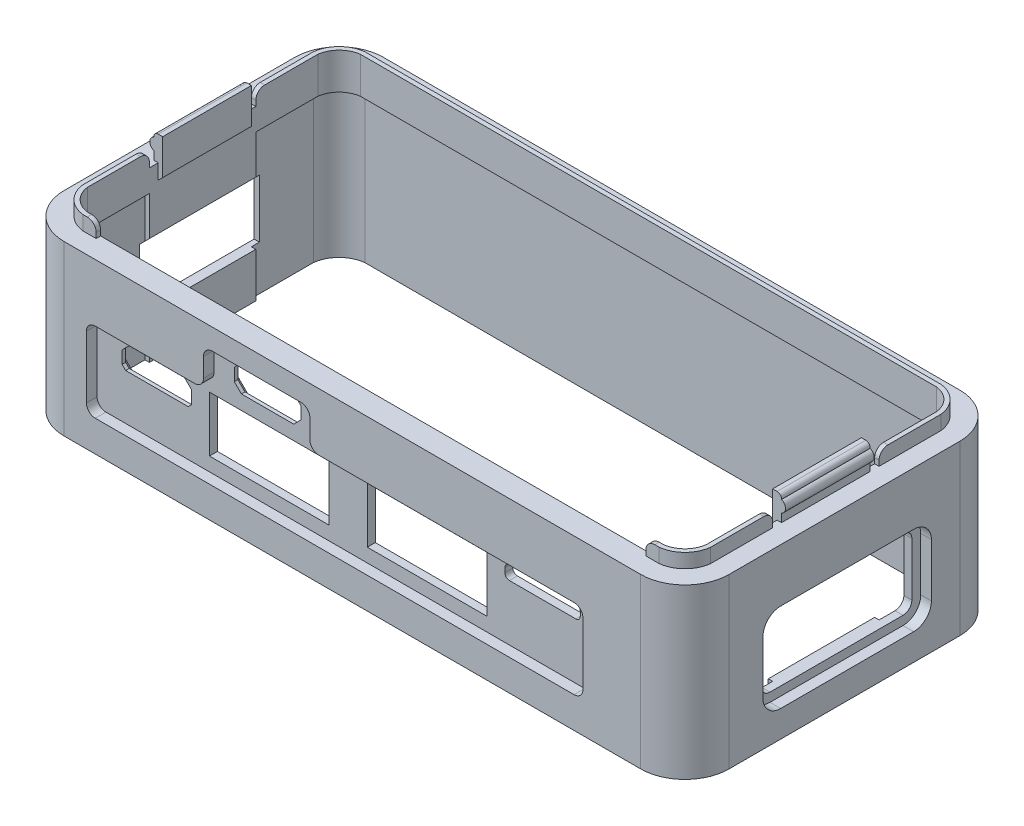
SolidWorks part; units mm, degrees
ref_plane "前视基准面" through (0, 0, 0) normal (0, 0, 1) x (1, 0, 0)
ref_plane "上视基准面" through (0, 0, 0) normal (0, 1, 0) x (1, 0, 0)
ref_plane "右视基准面" through (0, 0, 0) normal (1, 0, 0) x (0, 0, -1)
sketch "zero" plane through (0, 0, 0) normal (0, 1, 0) x (1, 0, 0)
  line L1 (-29.5, 15) -> (29.5, 15)
  line L2 (-32.5, 12) -> (-32.5, -12)
  line L3 (-29.5, -15) -> (29.5, -15)
  line L4 (32.5, 12) -> (32.5, -12)
  line L5 (-32.5, 15) -> (32.5, -15) construction
  line L6 (-32.5, -15) -> (32.5, 15) construction
  line L7 (-25.7, -15) -> (-14.5, -15)
  line L8 (-25.7, -15) -> (-25.7, -9.6569)
  line L9 (-25.7, -9.6569) -> (-14.5, -9.6569)
  line L10 (-14.5, -15) -> (-14.5, -9.6569)
  line L11 (5.2, -15) -> (12.7, -15)
  line L12 (5.2, -15) -> (5.2, -11)
  line L13 (5.2, -11) -> (12.7, -11)
  line L14 (12.7, -15) -> (12.7, -11)
  line L15 (17.8, -15) -> (25.3, -15)
  line L16 (17.8, -15) -> (17.8, -11)
  line L17 (17.8, -11) -> (25.3, -11)
  line L18 (25.3, -15) -> (25.3, -11)
  line L19 (-32.5, 7.7) -> (-19.5, 7.7)
  line L20 (-32.5, 7.7) -> (-32.5, -4.3)
  line L21 (-32.5, -4.3) -> (-19.5, -4.3)
  line L22 (-19.5, 7.7) -> (-19.5, -4.3)
  line L23 (-25.5, 14) -> (25.5, 14)
  line L24 (-25.5, 14) -> (-25.5, 8.8)
  line L25 (-25.5, 8.8) -> (25.5, 8.8)
  line L26 (25.5, 14) -> (25.5, 8.8)
  line L27 (-19.5, 7.2329) -> (-35.5, 7.2329)
  line L28 (-19.5, 7.2329) -> (-19.5, -3.7671)
  line L29 (-19.5, -3.7671) -> (-35.5, -3.7671)
  line L30 (-35.5, 7.2329) -> (-35.5, -3.7671)
  arc A0 (29.5, -15) -> (32.5, -12) centre (29.5, -12) ccw
  arc A1 (29.5, 15) -> (32.5, 12) centre (29.5, 12) cw
  arc A2 (-32.5, -12) -> (-29.5, -15) centre (-29.5, -12) ccw
  arc A3 (-29.5, 15) -> (-32.5, 12) centre (-29.5, 12) ccw
  circle A4 centre (-29, 11.4) radius 3
  circle A5 centre (-29, -11.5) radius 3
  circle A6 centre (29, 11.4) radius 3
  circle A7 centre (29, -11.5) radius 3
  circle A8 centre (-29, 11.4) radius 1.375
  circle A9 centre (-29, -11.5) radius 1.375
  circle A10 centre (29, -11.5) radius 1.375
  circle A11 centre (29, 11.4) radius 1.375
  point P0 (0, 0)
  dimension "D3" = 3
  dimension "D4" = 6
  dimension "D9" = 2.75
  dimension "D1" = 65
  dimension "D2" = 30
  dimension "D5" = 3.6
  dimension "D6" = 3.5
  dimension "D7" = 3.5
  dimension "D8" = 3.5
  dimension "D10" = 12
  dimension "D11" = 7.3
  dimension "D12" = 13
  dimension "D13" = 11.2
  dimension "D14" = 6.8
  dimension "D15" = 19.7
  dimension "D16" = 7.5
  dimension "D17" = 7.5
  dimension "D18" = 5.1
  dimension "D19" = 4
  dimension "D20" = 5.2
  dimension "D21" = 7
  dimension "D22" = 7
  dimension "D23" = 1
  dimension "D24" = 11
  dimension "D25" = 16
sketch "sugar" plane through (0, 0, 0) normal (0, 1, 0) x (1, 0, 0)
  line L1 (-29.5, 15) -> (29.5, 15)
  line L2 (-32.5, 12) -> (-32.5, -12)
  line L3 (-29.5, -15) -> (29.5, -15)
  line L4 (32.5, 12) -> (32.5, -12)
  line L5 (-32.5, 15) -> (32.5, -15) construction
  line L6 (-32.5, -15) -> (32.5, 15) construction
  line L7 (23.5, -11.5) -> (19.5, -11.5)
  line L8 (23.5, -11.5) -> (23.5, -13.9082)
  line L9 (23.5, -13.9082) -> (19.5, -13.9082)
  line L10 (19.5, -11.5) -> (19.5, -13.9082)
  line L11 (16, -11.0071) -> (8.5, -11.0071)
  line L12 (16, -11.0071) -> (16, -15)
  line L13 (16, -15) -> (8.5, -15)
  line L14 (8.5, -11.0071) -> (8.5, -15)
  line L15 (20.5, -13.9082) -> (22.5, -13.9082)
  line L16 (20.5, -13.9082) -> (20.5, -14.8173)
  line L17 (20.5, -14.8173) -> (22.5, -14.8173)
  line L18 (22.5, -13.9082) -> (22.5, -14.8173)
  arc A0 (29.5, 15) -> (32.5, 12) centre (29.5, 12) cw
  arc A1 (29.5, -15) -> (32.5, -12) centre (29.5, -12) ccw
  arc A2 (-32.5, -12) -> (-29.5, -15) centre (-29.5, -12) ccw
  arc A3 (-29.5, 15) -> (-32.5, 12) centre (-29.5, 12) ccw
  circle A4 centre (-29, 11.4) radius 3
  circle A5 centre (-29, 11.4) radius 1.375
  circle A6 centre (-29, -11.5) radius 3
  circle A7 centre (-29, -11.5) radius 1.375
  circle A8 centre (29, 11.4) radius 3
  circle A9 centre (29, 11.4) radius 1.375
  circle A10 centre (29, -11.5) radius 3
  circle A11 centre (29, -11.5) radius 1.375
  dimension "D3" = 3
  dimension "D1" = 65
  dimension "D2" = 30
  dimension "D4" = 9
  dimension "D5" = 4
  dimension "D6" = 3.5
  dimension "D7" = 7.5
  dimension "D8" = 2
  dimension "D9" = 1
sketch "case" plane through (0, 0, 0) normal (0, 1, 0) x (1, 0, 0)
  line L1 (-34.0422, 18) -> (30.9578, 18)
  line L2 (-39.0422, 13) -> (-39.0422, -13)
  line L3 (-34.0422, -18) -> (30.9578, -18)
  line L4 (35.9578, 13) -> (35.9578, -13)
  line L5 (-39.0422, 18) -> (35.9578, -18) construction
  line L6 (-39.0422, -18) -> (35.9578, 18) construction
  arc A0 (-39.0422, -13) -> (-34.0422, -18) centre (-34.0422, -13) ccw
  arc A1 (30.9578, -18) -> (35.9578, -13) centre (30.9578, -13) ccw
  arc A2 (30.9578, 18) -> (35.9578, 13) centre (30.9578, 13) cw
  arc A3 (-34.0422, 18) -> (-39.0422, 13) centre (-34.0422, 13) ccw
  point P0 (-1.5422, 0)
  point P3 (-1.5422, 0)
  dimension "D3" = 5
  dimension "D1" = 75
  dimension "D2" = 36
extrude "凸台-拉伸2" add sketch "case" along normal blind 19
sketch "草图2" plane through (0, 0, 0) normal (0, 1, 0) x (1, 0, 0)
  line L4 (-34.0422, -15.4) -> (30.9578, -15.4)
  line L5 (33.3578, -13) -> (33.3578, 13)
  line L6 (30.9578, 15.4) -> (-34.0422, 15.4)
  line L7 (-36.4422, 13) -> (-36.4422, -13)
  line L12 (33.8578, -13) -> (33.8578, 13)
  line L13 (30.9578, 15.9) -> (-34.0422, 15.9)
  line L14 (-36.9422, 13) -> (-36.9422, -13)
  line L15 (-34.0422, -15.9) -> (30.9578, -15.9)
  arc A4 (30.9578, -15.4) -> (33.3578, -13) centre (30.583, -12.6252) ccw
  arc A5 (33.3578, 13) -> (30.9578, 15.4) centre (30.583, 12.6252) ccw
  arc A6 (-34.0422, 15.4) -> (-36.4422, 13) centre (-33.6674, 12.6252) ccw
  arc A7 (-36.4422, -13) -> (-34.0422, -15.4) centre (-33.6674, -12.6252) ccw
  arc A12 (30.9578, -15.9) -> (33.8578, -13) centre (30.5796, -12.6217) ccw
  arc A13 (33.8578, 13) -> (30.9578, 15.9) centre (30.5796, 12.6217) ccw
  arc A14 (-34.0422, 15.9) -> (-36.9422, 13) centre (-33.6639, 12.6217) ccw
  arc A15 (-36.9422, -13) -> (-34.0422, -15.9) centre (-33.6639, -12.6217) ccw
ref_plane "基准面1" through (0, 19, 0) normal (0, 1, 0) x (1, 0, 0)
sketch "草图3" plane through (0, 19, 0) normal (0, 1, 0) x (1, 0, 0)
  line L4 (-34.0422, -15.4) -> (30.9578, -15.4)
  line L5 (33.3578, -13) -> (33.3578, 13)
  line L6 (30.9578, 15.4) -> (-34.0422, 15.4)
  line L7 (-36.4422, 13) -> (-36.4422, -13)
  line L8 (-34.0422, -15.4) -> (30.9578, -15.4)
  line L9 (33.3578, -13) -> (33.3578, 13)
  line L10 (30.9578, 15.4) -> (-34.0422, 15.4)
  line L11 (-36.4422, 13) -> (-36.4422, -13)
  line L12 (-36.9422, 13) -> (-36.9422, -13)
  line L13 (-34.0422, -15.9) -> (30.9578, -15.9)
  line L14 (33.8578, -13) -> (33.8578, 13)
  line L15 (30.9578, 15.9) -> (-34.0422, 15.9)
  line L16 (-36.9422, 13) -> (-36.9422, -13)
  line L17 (-34.0422, -15.9) -> (30.9578, -15.9)
  line L18 (33.8578, -13) -> (33.8578, 13)
  line L19 (30.9578, 15.9) -> (-34.0422, 15.9)
  arc A4 (30.9578, -15.4) -> (33.3578, -13) centre (30.583, -12.6252) ccw
  arc A5 (33.3578, 13) -> (30.9578, 15.4) centre (30.583, 12.6252) ccw
  arc A6 (-34.0422, 15.4) -> (-36.4422, 13) centre (-33.6674, 12.6252) ccw
  arc A7 (-36.4422, -13) -> (-34.0422, -15.4) centre (-33.6674, -12.6252) ccw
  arc A8 (30.9578, -15.4) -> (33.3578, -13) centre (30.583, -12.6252) ccw
  arc A9 (33.3578, 13) -> (30.9578, 15.4) centre (30.583, 12.6252) ccw
  arc A10 (-34.0422, 15.4) -> (-36.4422, 13) centre (-33.6674, 12.6252) ccw
  arc A11 (-36.4422, -13) -> (-34.0422, -15.4) centre (-33.6674, -12.6252) ccw
  arc A12 (-36.9422, -13) -> (-34.0422, -15.9) centre (-33.6639, -12.6217) ccw
  arc A13 (30.9578, -15.9) -> (33.8578, -13) centre (30.5796, -12.6217) ccw
  arc A14 (33.8578, 13) -> (30.9578, 15.9) centre (30.5796, 12.6217) ccw
  arc A15 (-34.0422, 15.9) -> (-36.9422, 13) centre (-33.6639, 12.6217) ccw
  arc A16 (-36.9422, -13) -> (-34.0422, -15.9) centre (-33.6639, -12.6217) ccw
  arc A17 (30.9578, -15.9) -> (33.8578, -13) centre (30.5796, -12.6217) ccw
  arc A18 (33.8578, 13) -> (30.9578, 15.9) centre (30.5796, 12.6217) ccw
  arc A19 (-34.0422, 15.9) -> (-36.9422, 13) centre (-33.6639, 12.6217) ccw
  dimension "D1" = 0
  dimension "D2" = 0
extrude "凸台-拉伸4" add sketch "草图3" along normal blind 1.6
ref_plane "基准面3" through (33.8578, 0, 0) normal (1, 0, 0) x (0, 0, -1)
ref_plane "基准面7" through (-36.9422, 0, 0) normal (-1, 0, 0) x (0, 0, 1)
ref_plane "基准面8" through (0, 0, 0) normal (0, -1, 0) x (-1, 0, 0)
sketch "草图14" plane through (0, 19, 0) normal (0, 1, 0) x (1, 0, 0)
  line L4 (-34.0422, -15.4) -> (30.9578, -15.4)
  line L5 (33.3578, -13) -> (33.3578, 13)
  line L6 (30.9578, 15.4) -> (-34.0422, 15.4)
  line L7 (-36.4422, 13) -> (-36.4422, -13)
  line L8 (-34.0422, -15.4) -> (30.9578, -15.4)
  line L9 (33.3578, -13) -> (33.3578, 13)
  line L10 (30.9578, 15.4) -> (-34.0422, 15.4)
  line L11 (-36.4422, 13) -> (-36.4422, -13)
  arc A4 (30.9578, -15.4) -> (33.3578, -13) centre (30.583, -12.6252) ccw
  arc A5 (33.3578, 13) -> (30.9578, 15.4) centre (30.583, 12.6252) ccw
  arc A6 (-34.0422, 15.4) -> (-36.4422, 13) centre (-33.6674, 12.6252) ccw
  arc A7 (-36.4422, -13) -> (-34.0422, -15.4) centre (-33.6674, -12.6252) ccw
  arc A8 (30.9578, -15.4) -> (33.3578, -13) centre (30.583, -12.6252) ccw
  arc A9 (33.3578, 13) -> (30.9578, 15.4) centre (30.583, 12.6252) ccw
  arc A10 (-34.0422, 15.4) -> (-36.4422, 13) centre (-33.6674, 12.6252) ccw
  arc A11 (-36.4422, -13) -> (-34.0422, -15.4) centre (-33.6674, -12.6252) ccw
  dimension "D1" = 0
extrude "切除-拉伸2" cut sketch "草图14" against normal blind 19
sketch "草图17" plane through (0, 0, 18) normal (0, 0, 1) x (1, 0, 0)
  line L0 (-34.0422, 0) -> (30.9578, 0) construction
  line L1 (12.4359, 5.0443) -> (-1.0641, 5.0443)
  line L2 (12.4359, 5.0443) -> (12.4359, 11.2943)
  line L3 (12.4359, 11.2943) -> (-1.0641, 11.2943)
  line L4 (-1.0641, 5.0443) -> (-1.0641, 11.2943)
  line L5 (-5.3641, 5.0443) -> (-18.8641, 5.0443)
  line L6 (-5.3641, 5.0443) -> (-5.3641, 11.2943)
  line L7 (-5.3641, 11.2943) -> (-18.8641, 11.2943)
  line L8 (-18.8641, 5.0443) -> (-18.8641, 11.2943)
  line L9 (-20.8641, 8.6743) -> (-28.7141, 8.6743)
  line L10 (-20.8641, 8.6743) -> (-20.8641, 11.2943)
  line L11 (-20.8641, 11.2943) -> (-28.7141, 11.2943)
  line L12 (-28.7141, 8.6743) -> (-28.7141, 11.2943)
  line L13 (35.9578, 19) -> (35.9578, 0) construction
  line L14 (-39.0422, 19) -> (-39.0422, 0) construction
  line L15 (-8.5641, 12.9143) -> (-16.0641, 12.9143)
  line L16 (-8.5641, 12.9143) -> (-8.5641, 15.5343)
  line L17 (-8.5641, 15.5343) -> (-16.0641, 15.5343)
  line L18 (-16.0641, 12.9143) -> (-16.0641, 15.5343)
  dimension "D1" = 13.5
  dimension "D2" = 13.5
  dimension "D3" = 4.3
  dimension "D4" = 6.25
  dimension "D5" = 6.25
  dimension "D6" = 5.0443
  dimension "D7" = 23.5219
  dimension "D8" = 7.85
  dimension "D9" = 2.62
  dimension "D10" = 2
  dimension "D11" = 8.6743
  dimension "D12" = 7.5
  dimension "D13" = 2.62
  dimension "D14" = 1.62
  dimension "D15" = 22.9781
extrude "切除-拉伸4" cut sketch "草图17" against normal blind 2.62
sketch "草图18" plane through (-39.0422, 0, 0) normal (-1, 0, 0) x (0, 0, 1)
  line L0 (18, 19) -> (18, 0) construction
  line L1 (6.5862, 5.0443) -> (-6.9138, 5.0443)
  line L2 (6.5862, 5.0443) -> (6.5862, 11.2943)
  line L3 (6.5862, 11.2943) -> (-6.9138, 11.2943)
  line L4 (-6.9138, 5.0443) -> (-6.9138, 11.2943)
  line L5 (-13, 0) -> (13, 0) construction
  dimension "D1" = 13.5
  dimension "D2" = 6.25
  dimension "D3" = 11.4138
  dimension "D4" = 5.0443
extrude "切除-拉伸5" cut sketch "草图18" against normal up to next
sketch "草图19" plane through (35.9578, 0, 0) normal (1, 0, 0) x (0, 0, -1)
  line L0 (-13, 0) -> (13, 0) construction
  line L1 (8.8, 4) -> (-8.2, 4)
  line L2 (8.8, 4) -> (8.8, 12)
  line L3 (8.8, 12) -> (-8.2, 12)
  line L4 (-8.2, 4) -> (-8.2, 12)
  line L5 (8.8, 4) -> (-8.2, 12) construction
  line L6 (8.8, 12) -> (-8.2, 4) construction
  line L7 (18, 19) -> (18, 0) construction
  point P0 (0.3, 8)
  dimension "D1" = 17
  dimension "D2" = 8
  dimension "D3" = 8
  dimension "D4" = 17.7
extrude "切除-拉伸6" cut sketch "草图19" against normal up to next
chamfer "倒角1" distance 0.4 angle 45 4 edges at (-8.5641, 15.5343, 16.7) (-16.0641, 15.5343, 16.7) (-28.7141, 8.6743, 16.7) (-20.8641, 8.6743, 16.7)
chamfer "倒角2" distance 0.8 angle 45 4 edges at (-28.7141, 11.2943, 16.7) (-20.8641, 11.2943, 16.7) (-16.0641, 12.9143, 16.7) (-8.5641, 12.9143, 16.7)
sketch "草图21" plane through (0, 0, 18) normal (0, 0, 1) x (1, 0, 0)
  line L0 (30.9578, 0) -> (35.9578, 0) construction
  line L1 (24.4578, 3.5) -> (-31.5422, 3.5)
  line L2 (24.4578, 3.5) -> (24.4578, 12.5)
  line L3 (24.4578, 12.5) -> (-31.5422, 12.5)
  line L4 (-31.5422, 3.5) -> (-31.5422, 12.5)
  line L5 (35.9578, 19) -> (35.9578, 0) construction
  dimension "D1" = 56
  dimension "D2" = 9
  dimension "D3" = 3.5
  dimension "D4" = 11.5
extrude "切除-拉伸8" cut sketch "草图21" against normal blind 1.2
sketch "草图22" plane through (0, 0, 18) normal (0, 0, 1) x (1, 0, 0)
  line L0 (24.4578, 12.5) -> (-31.5422, 12.5) construction
  line L1 (-6.3422, 12.5) -> (-18.3422, 12.5)
  line L2 (-6.3422, 12.5) -> (-6.3422, 16.6481)
  line L3 (-6.3422, 16.6481) -> (-18.3422, 16.6481)
  line L4 (-18.3422, 12.5) -> (-18.3422, 16.6481)
  line L5 (-34.0422, 19) -> (30.9578, 19) construction
  line L6 (35.9578, 19) -> (35.9578, 0) construction
  dimension "D1" = 12
  dimension "D2" = 2.3519
  dimension "D3" = 42.3
extrude "切除-拉伸9" cut sketch "草图22" against normal blind 1.2
sketch "草图23" plane through (-39.0422, 0, 0) normal (-1, 0, 0) x (0, 0, 1)
  line L0 (-6.9138, 5.0443) -> (6.5862, 5.0443) construction
  line L1 (9.3362, 3.1562) -> (-9.6638, 3.1562)
  line L2 (9.3362, 3.1562) -> (9.3362, 13.1562)
  line L3 (9.3362, 13.1562) -> (-9.6638, 13.1562)
  line L4 (-9.6638, 3.1562) -> (-9.6638, 13.1562)
  line L5 (9.3362, 3.1562) -> (-9.6638, 13.1562) construction
  line L6 (9.3362, 13.1562) -> (-9.6638, 3.1562) construction
  point P0 (-0.1638, 8.1562)
  point P8 (-0.1638, 5.0443)
  dimension "D1" = 19
  dimension "D2" = 10
extrude "切除-拉伸10" cut sketch "草图23" against normal blind 1.5
fillet "圆角2" radius 1 16 edges at (-38.2922, 13.1562, -9.6638) (-38.2922, 3.1562, -9.6638) (-38.2922, 3.1562, 9.3362) (-38.2922, 13.1562, 9.3362) (-31.5422, 3.5, 17.4) (-31.5422, 12.5, 17.4) (-18.3422, 12.5, 17.4) (-18.3422, 16.6481, 17.4) (-6.3422, 16.6481, 17.4) (-6.3422, 12.5, 17.4) (24.4578, 3.5, 17.4) (24.4578, 12.5, 17.4) (34.6578, 12, 8.2) (34.6578, 4, 8.2) (34.6578, 4, -8.8) (34.6578, 12, -8.8)
sketch "草图24" plane through (35.9578, 0, 0) normal (1, 0, 0) x (0, 0, -1)
  line L8 (-9.2, 11) -> (-9.2, 5)
  line L9 (7.8, 13) -> (-7.2, 13)
  line L10 (9.8, 5) -> (9.8, 11)
  line L11 (-7.2, 3) -> (7.8, 3)
  line L12 (-9.2, 11) -> (-9.2, 5)
  line L13 (7.8, 13) -> (-7.2, 13)
  line L14 (9.8, 5) -> (9.8, 11)
  line L15 (-7.2, 3) -> (7.8, 3)
  arc A8 (-9.2, 5) -> (-7.2, 3) centre (-7.2, 5) ccw
  arc A9 (-7.2, 13) -> (-9.2, 11) centre (-7.2, 11) ccw
  arc A10 (9.8, 11) -> (7.8, 13) centre (7.8, 11) ccw
  arc A11 (7.8, 3) -> (9.8, 5) centre (7.8, 5) ccw
  arc A12 (-9.2, 5) -> (-7.2, 3) centre (-7.2, 5) ccw
  arc A13 (-7.2, 13) -> (-9.2, 11) centre (-7.2, 11) ccw
  arc A14 (9.8, 11) -> (7.8, 13) centre (7.8, 11) ccw
  arc A15 (7.8, 3) -> (9.8, 5) centre (7.8, 5) ccw
  dimension "D1" = 1
extrude "切除-拉伸11" cut sketch "草图24" against normal blind 1.2
sketch "草图25" plane through (0, 20.6, 0) normal (0, 1, 0) x (1, 0, 0)
  line L0 (-34.0422, -15.4) -> (30.9578, -15.4) construction
  line L1 (-32.5422, -15.4) -> (29.4578, -15.4)
  line L2 (-32.5422, -15.4) -> (-32.5422, -15.9)
  line L3 (-32.5422, -15.9) -> (29.4578, -15.9)
  line L4 (29.4578, -15.4) -> (29.4578, -15.9)
  line L5 (-34.0422, -15.9) -> (30.9578, -15.9) construction
  line L7 (-34.0422, -18) -> (30.9578, -18) construction
  point P8 (-1.5422, -15.4)
  point P11 (-1.5422, -18)
  dimension "D1" = 62
extrude "切除-拉伸12" cut sketch "草图25" against normal blind 1.6
fillet "圆角3" radius 1 2 edges at (-32.5422, 20.6, 15.65) (29.4578, 20.6, 15.65)
sketch "草图26" plane through (0, 20.6, 0) normal (0, 1, 0) x (1, 0, 0)
  line L0 (33.3578, -13) -> (33.3578, 13) construction
  line L1 (33.3578, 5) -> (33.8578, 5)
  line L2 (33.3578, 5) -> (33.3578, -5)
  line L3 (33.3578, -5) -> (33.8578, -5)
  line L4 (33.8578, 5) -> (33.8578, -5)
  line L5 (33.8578, -13) -> (33.8578, 13) construction
  line L6 (-36.9422, 13) -> (-36.9422, -13) construction
  line L7 (-36.9422, 5) -> (-36.4422, 5)
  line L8 (-36.9422, 5) -> (-36.9422, -5)
  line L9 (-36.9422, -5) -> (-36.4422, -5)
  line L10 (-36.4422, 5) -> (-36.4422, -5)
  line L11 (-36.4422, 13) -> (-36.4422, -13) construction
  line L13 (-39.0422, 13) -> (-39.0422, -13) construction
  point P16 (-39.0422, 0)
  point P21 (-36.4422, 0)
  point P22 (33.3578, 0)
  dimension "D1" = 10
  dimension "D2" = 10
extrude "凸台-拉伸5" add sketch "草图26" along normal blind 1.2
sketch "草图27" plane through (0, 0, 5) normal (0, 0, 1) x (1, 0, 0)
  line L0 (33.8578, 19) -> (30.9578, 19) construction
  line L1 (33.8578, 21.8) -> (33.8578, 20.6) construction
  line L2 (-36.9422, 21.8) -> (-36.9422, 20.6) construction
  circle A0 centre (33.6078, 20.6) radius 0.7
  circle A1 centre (-36.6922, 20.6) radius 0.7
  dimension "D1" = 1.4
  dimension "D2" = 1.4
  dimension "D3" = 1.6
  dimension "D4" = 1.6
  dimension "D5" = 0.25
  dimension "D6" = 0.25
extrude "凸台-拉伸6" add sketch "草图27" against normal blind 10
sketch "草图28" plane through (0, 20.6, 0) normal (0, 1, 0) x (1, 0, 0)
  line L1 (33.8578, -5) -> (33.3578, -5)
  line L2 (33.8578, -5) -> (33.8578, -6)
  line L3 (33.8578, -6) -> (33.3578, -6)
  line L4 (33.3578, -5) -> (33.3578, -6)
  line L5 (33.3578, 5) -> (33.3578, 13) construction
  line L6 (33.8578, 5) -> (33.3578, 5)
  line L7 (33.8578, 5) -> (33.8578, 6)
  line L8 (33.8578, 6) -> (33.3578, 6)
  line L9 (33.3578, 5) -> (33.3578, 6)
  line L10 (-36.9422, -5) -> (-36.9422, -13) construction
  line L11 (-36.4422, -5) -> (-36.9422, -5)
  line L12 (-36.4422, -5) -> (-36.4422, -6)
  line L13 (-36.4422, -6) -> (-36.9422, -6)
  line L14 (-36.9422, -5) -> (-36.9422, -6)
  line L15 (-36.9422, 13) -> (-36.9422, -13) construction
  line L16 (-36.4422, 5) -> (-36.9422, 5)
  line L17 (-36.4422, 5) -> (-36.4422, 6)
  line L18 (-36.4422, 6) -> (-36.9422, 6)
  line L19 (-36.9422, 5) -> (-36.9422, 6)
  point P5 (0, 0)
  point P28 (0, 0)
  dimension "D1" = 1
  dimension "D2" = 1
  dimension "D3" = 1
  dimension "D4" = 1
extrude "切除-拉伸13" cut sketch "草图28" against normal blind 1.6
fillet "圆角4" radius 1 4 edges at (33.6078, 20.6, -6) (33.6078, 20.6, 6) (-36.6922, 20.6, 6) (-36.6922, 20.6, -6)
sketch "草图29" plane through (33.3578, 0, 0) normal (-1, 0, 0) x (0, 0, 1)
  line L1 (-5, 21.8) -> (5, 21.8)
  line L2 (-5, 21.8) -> (-5, 16.8)
  line L3 (-5, 16.8) -> (5, 16.8)
  line L4 (5, 21.8) -> (5, 16.8)
  dimension "D1" = 10
  dimension "D2" = 5
extrude "凸台-拉伸7" add sketch "草图29" along normal blind 0.5
sketch "草图30" plane through (-36.4422, 0, 0) normal (1, 0, 0) x (0, 0, -1)
  line L1 (-5, 21.8) -> (5, 21.8)
  line L2 (-5, 21.8) -> (-5, 16.8)
  line L3 (-5, 16.8) -> (5, 16.8)
  line L4 (5, 21.8) -> (5, 16.8)
  dimension "D1" = 10
  dimension "D2" = 5
extrude "凸台-拉伸8" add sketch "草图30" along normal blind 0.5
fillet "圆角5" radius 0.5 2 edges at (33.8578, 21.8, 0) (-36.9422, 21.8, 0)
chamfer "倒角3" distance 1 angle 45 2 edges at (-35.9422, 16.8, 0) (32.8578, 16.8, 0)
sketch "草图32" plane through (0, 0, 18) normal (0, 0, 1) x (1, 0, 0)
  line L0 (35.9578, 19) -> (35.9578, 0) construction
  line L1 (22.9578, 9.8) -> (14.4578, 9.8)
  line L2 (22.9578, 9.8) -> (22.9578, 11.3)
  line L3 (22.9578, 11.3) -> (14.4578, 11.3)
  line L4 (14.4578, 9.8) -> (14.4578, 11.3)
  dimension "D1" = 8.5
  dimension "D2" = 1.5
  dimension "D3" = 9.8
  dimension "D4" = 13
extrude "切除-拉伸14" cut sketch "草图32" against normal up to next
fillet "圆角6" radius 0.5 4 edges at (14.4578, 11.3, 16.1) (14.4578, 9.8, 16.1) (22.9578, 9.8, 16.1) (22.9578, 11.3, 16.1)
sketch "草图36" plane through (0, 0, 0) normal (0, 1, 0) x (1, 0, 0)
  line L1 (29.4578, -15.4) -> (-32.5422, -15.4) construction
  line L2 (-32.5422, -15.4) -> (-33.5422, -15.4) construction
  line L3 (-33.5422, -15.9) -> (-32.5422, -15.9) construction
  line L4 (-36.4422, -13) -> (-36.4422, -7) construction
  line L5 (-36.9422, -7) -> (-36.9422, -13) construction
  line L6 (-34.0422, -15.9) -> (-33.5422, -15.9) construction
  line L7 (-33.5422, -15.4) -> (-34.0422, -15.4) construction
  line L8 (-36.9422, -6) -> (-36.9422, -7) construction
  line L9 (-36.4422, -7) -> (-36.4422, -6) construction
  line L10 (-36.4422, -6) -> (-36.9422, -6) construction
  line L11 (29.4578, -15.9) -> (30.4578, -15.9) construction
  line L12 (30.4578, -15.4) -> (29.4578, -15.4) construction
  line L13 (33.8578, -13) -> (33.8578, -7) construction
  line L14 (33.3578, -7) -> (33.3578, -13) construction
  line L15 (30.9578, -15.4) -> (30.4578, -15.4) construction
  line L16 (30.4578, -15.9) -> (30.9578, -15.9) construction
  line L17 (33.3578, -6) -> (33.3578, -7) construction
  line L18 (33.8578, -7) -> (33.8578, -6) construction
  line L19 (33.8578, -6) -> (33.3578, -6) construction
  line L20 (33.8578, 6) -> (33.8578, 7) construction
  line L21 (33.3578, 7) -> (33.3578, 6) construction
  line L22 (33.3578, 6) -> (33.8578, 6) construction
  line L23 (-36.4422, 6) -> (-36.4422, 7) construction
  line L24 (-36.9422, 7) -> (-36.9422, 6) construction
  line L25 (-36.9422, 6) -> (-36.4422, 6) construction
  line L26 (33.3578, 13) -> (33.3578, 7) construction
  line L27 (33.8578, 7) -> (33.8578, 13) construction
  line L28 (30.9578, 15.9) -> (-34.0422, 15.9) construction
  line L29 (-36.9422, 13) -> (-36.9422, 7) construction
  line L30 (-36.4422, 7) -> (-36.4422, 13) construction
  line L31 (-34.0422, 15.4) -> (30.9578, 15.4) construction
  line L32 (-32.5422, -15.9) -> (29.4578, -15.9)
  line L33 (29.4578, -15.4) -> (-32.5422, -15.4)
  line L34 (-32.5422, -15.4) -> (-33.5422, -15.4)
  line L35 (-33.5422, -15.9) -> (-32.5422, -15.9)
  line L36 (-36.4422, -13) -> (-36.4422, -7)
  line L37 (-36.9422, -7) -> (-36.9422, -13)
  line L38 (-34.0422, -15.9) -> (-33.5422, -15.9)
  line L39 (-33.5422, -15.4) -> (-34.0422, -15.4)
  line L40 (-36.9422, -6) -> (-36.9422, -7)
  line L41 (-36.4422, -7) -> (-36.4422, -6)
  line L42 (-36.4422, -6) -> (-36.9422, -6)
  line L43 (29.4578, -15.9) -> (30.4578, -15.9)
  line L44 (30.4578, -15.4) -> (29.4578, -15.4)
  line L45 (33.8578, -13) -> (33.8578, -7)
  line L46 (33.3578, -7) -> (33.3578, -13)
  line L47 (30.9578, -15.4) -> (30.4578, -15.4)
  line L48 (30.4578, -15.9) -> (30.9578, -15.9)
  line L49 (33.3578, -6) -> (33.3578, -7)
  line L50 (33.8578, -7) -> (33.8578, -6)
  line L51 (33.8578, -6) -> (33.3578, -6)
  line L52 (33.8578, 6) -> (33.8578, 7)
  line L53 (33.3578, 7) -> (33.3578, 6)
  line L54 (33.3578, 6) -> (33.8578, 6)
  line L55 (-36.4422, 6) -> (-36.4422, 7)
  line L56 (-36.9422, 7) -> (-36.9422, 6)
  line L57 (-36.9422, 6) -> (-36.4422, 6)
  line L58 (33.3578, 13) -> (33.3578, 7)
  line L59 (33.8578, 7) -> (33.8578, 13)
  line L60 (30.9578, 15.9) -> (-34.0422, 15.9)
  line L61 (-36.9422, 13) -> (-36.9422, 7)
  line L62 (-36.4422, 7) -> (-36.4422, 13)
  line L63 (-34.0422, 15.4) -> (30.9578, 15.4)
  arc A0 (-36.9422, -13) -> (-34.0422, -15.9) centre (-33.6639, -12.6217) ccw construction
  arc A1 (-36.4422, -13) -> (-34.0422, -15.4) centre (-33.6674, -12.6252) ccw construction
  arc A2 (30.9578, -15.4) -> (33.3578, -13) centre (30.583, -12.6252) ccw construction
  arc A3 (30.9578, -15.9) -> (33.8578, -13) centre (30.5796, -12.6217) ccw construction
  arc A4 (33.8578, 13) -> (30.9578, 15.9) centre (30.5796, 12.6217) ccw construction
  arc A5 (-34.0422, 15.9) -> (-36.9422, 13) centre (-33.6639, 12.6217) ccw construction
  arc A6 (-34.0422, 15.4) -> (-36.4422, 13) centre (-33.6674, 12.6252) ccw construction
  arc A7 (33.3578, 13) -> (30.9578, 15.4) centre (30.583, 12.6252) ccw construction
  arc A8 (-36.9422, -13) -> (-34.0422, -15.9) centre (-33.6639, -12.6217) ccw
  arc A9 (-36.4422, -13) -> (-34.0422, -15.4) centre (-33.6674, -12.6252) ccw
  arc A10 (30.9578, -15.4) -> (33.3578, -13) centre (30.583, -12.6252) ccw
  arc A11 (30.9578, -15.9) -> (33.8578, -13) centre (30.5796, -12.6217) ccw
  arc A12 (33.8578, 13) -> (30.9578, 15.9) centre (30.5796, 12.6217) ccw
  arc A13 (-34.0422, 15.9) -> (-36.9422, 13) centre (-33.6639, 12.6217) ccw
  arc A14 (-34.0422, 15.4) -> (-36.4422, 13) centre (-33.6674, 12.6252) ccw
  arc A15 (33.3578, 13) -> (30.9578, 15.4) centre (30.583, 12.6252) ccw
  point P4 (0, 0)
  point P7 (0, 0)
  point P13 (0, 0)
  point P15 (0, 0)
extrude "切除-拉伸18" cut sketch "草图36" along normal blind 16.5
chamfer "倒角5" distance 0.5 angle 45 16 edges at (-21.0641, 8.8743, 15.9) (-20.8641, 9.7843, 15.9) (-21.2641, 10.8943, 15.9) (-24.7891, 11.2943, 15.9) (-28.3141, 10.8943, 15.9) (-28.7141, 9.7843, 15.9) (-28.5141, 8.8743, 15.9) (-24.7891, 8.6743, 15.9) (-16.0641, 14.4243, 15.9) (-15.8641, 15.3343, 15.9) (-12.3141, 15.5343, 15.9) (-8.7641, 15.3343, 15.9) (-15.6641, 13.3143, 15.9) (-12.3141, 12.9143, 15.9) (-8.9641, 13.3143, 15.9) (-8.5641, 14.4243, 15.9)
chamfer "倒角6" distance 0.8 angle 45 1 edges at (-36.4422, 11.2943, 0)
